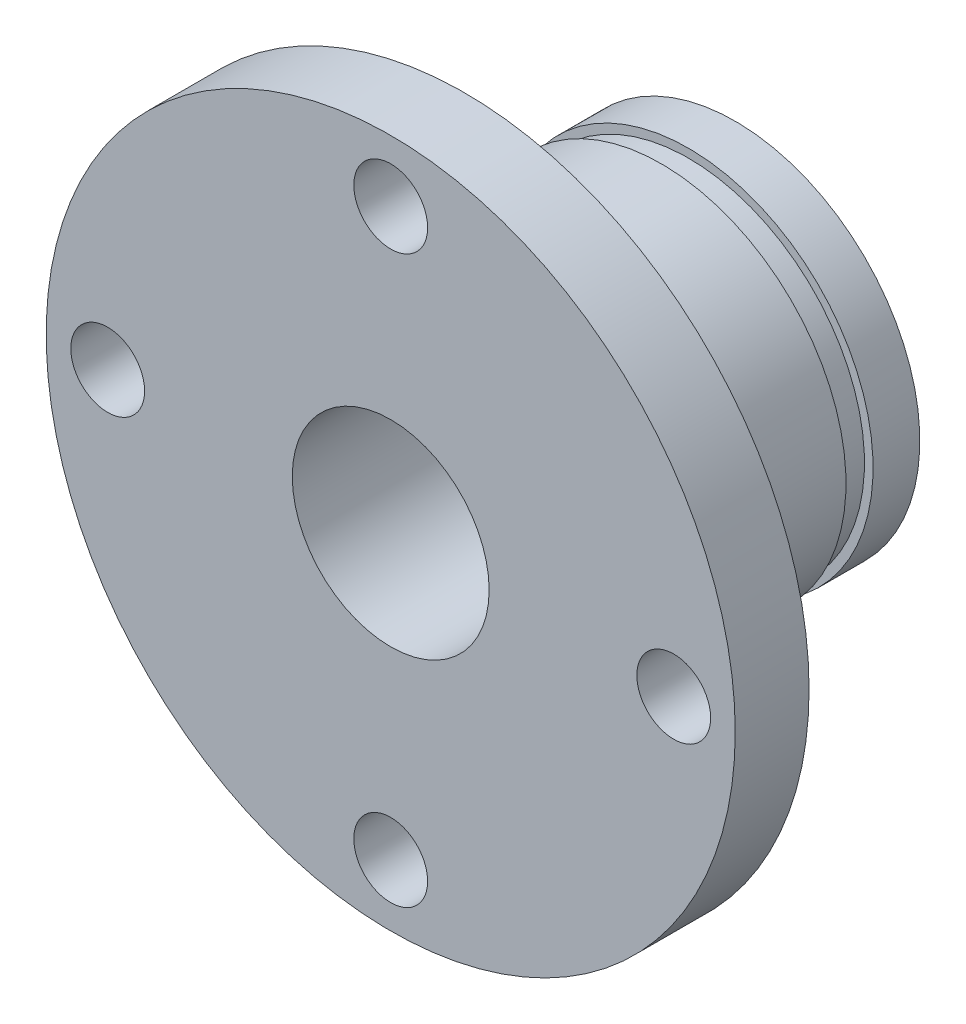
SolidWorks part; units mm, degrees
material "6061 合金"
ref_plane "前视基准面" through (0, 0, 0) normal (0, 0, 1) x (1, 0, 0)
ref_plane "上视基准面" through (0, 0, 0) normal (0, 1, 0) x (1, 0, 0)
ref_plane "右视基准面" through (0, 0, 0) normal (1, 0, 0) x (0, 0, -1)
sketch "草图1" plane through (0, 0, 0) normal (0, 0, 1) x (1, 0, 0)
  line L0 (0, 0) -> (-3, 0) construction
  circle A1 centre (0, 0) radius 14
  circle A2 centre (0, 0) radius 11.5 construction
  circle A3 centre (0, 11.5) radius 1.5
  circle A4 centre (11.5, 0) radius 1.5
  circle A5 centre (0, -11.5) radius 1.5
  circle A6 centre (-11.5, 0) radius 1.5
  circle A7 centre (0, 0) radius 4
  point P18 (0, 0)
  dimension "D1" = 4
extrude "凸台-拉伸1" add sketch "草图1" along normal blind 3
sketch "草图2" plane through (0, 0, 0) normal (0, 0, -1) x (-1, 0, 0)
  circle A0 centre (0, 0) radius 9
  circle A3 centre (0, 0) radius 4
extrude "凸台-拉伸2" add sketch "草图2" along normal blind 1
sketch "草图3" plane through (0, 0, -1) normal (0, 0, -1) x (-1, 0, 0)
  circle A0 centre (0, 0) radius 7.5
  circle A3 centre (0, 0) radius 4
extrude "凸台-拉伸3" add sketch "草图3" along normal blind 10
ref_plane "基准面1" through (0, 0, -8) normal (0, 0, -1) x (-1, 0, 0)
sketch "草图4" plane through (0, 0, -8) normal (0, 0, -1) x (-1, 0, 0)
  circle A0 centre (0, 0) radius 7.15
  circle A1 centre (0, 0) radius 7.5
extrude "切除-拉伸2" cut sketch "草图4" along normal blind 1.1
chamfer "倒角1" distance 0.2 angle 45 1 edges at (9, 0, 0)
